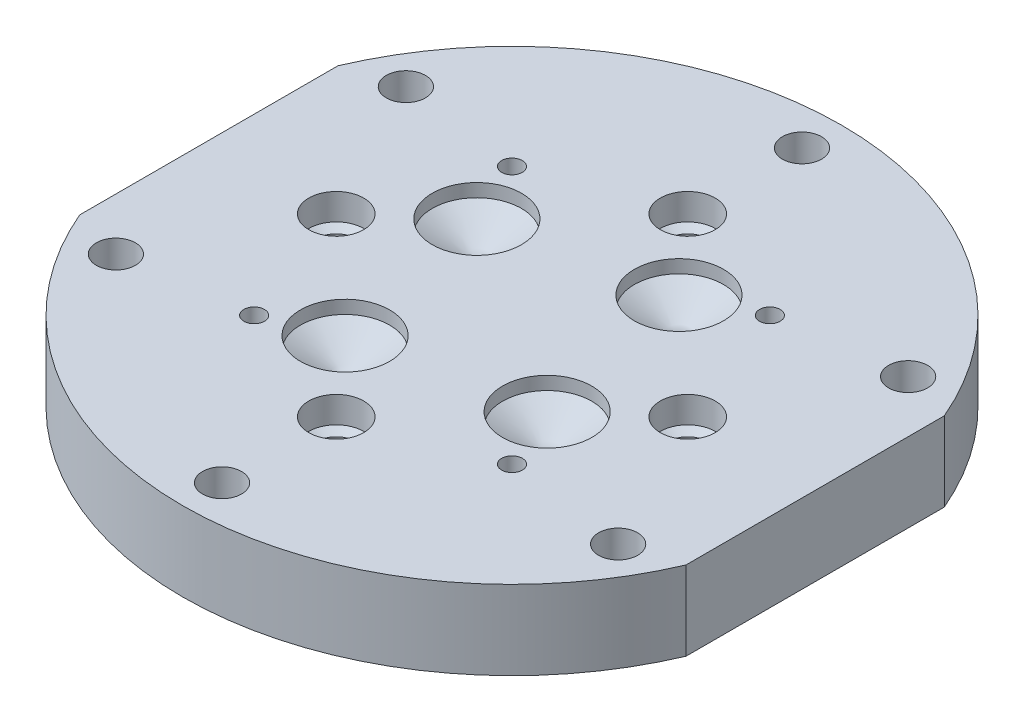
SolidWorks part; units mm, degrees
material "Copper"
ref_plane "Front Plane" through (0, 0, 0) normal (0, 0, 1) x (1, 0, 0)
ref_plane "Top Plane" through (0, 0, 0) normal (0, 1, 0) x (1, 0, 0)
ref_plane "Right Plane" through (0, 0, 0) normal (1, 0, 0) x (0, 0, -1)
ref_axis "Y Axis" through (0, 0.1588, 0) along (0, -1, 0)
sketch "outer" plane through (0, 0, 0) normal (0, 1, 0) x (1, 0, 0)
  circle A0 centre (0, 0) radius 19.05
  dimension "D1" = 38.1
extrude "Body" add sketch "outer" against normal blind 4.572
sketch "Screw Position" plane through (0, 0, 0) normal (0, 1, 0) x (1, 0, 0)
  point P0 (0, -16.764)
  dimension "D1" = 16.764
hole_wizard "#4-40 Tapped Hole" positions "Sketch12" profile "Sketch13" tap size "#4-40" standard "ANSI Inch" end condition through all
sketch "Sketch12" plane through (0, 0, 0) normal (0, 1, 0) x (1, 0, 0)
  point P0 (0, -16.764)
sketch "Sketch13" plane through (0, 0, 16.764) normal (1, 0, 0) x (0, 0, 1)
  line L0 (0, 0) -> (0, 4.572)
  line L1 (0, 4.572) -> (1.1303, 4.572)
  line L2 (1.1303, 4.572) -> (1.1303, 0)
  line L5 (1.1303, 0) -> (0, 0)
  line L11 (0, -6.35) -> (0, 107.95) construction
  dimension "Thru Tap Drill Dia." = 2.2606
  dimension "Thru Tap Drill Depth" = 4.572
cosmetic thread "Hole Thread3" parameters "D2"=2.8448
pattern_circular "Screw Holes" count 6 over 360 about axis through (0, 0.1588, 0) along (0, -1, 0) of "#4-40 Tapped Hole"
sketch "inner" plane through (0, 0, 0) normal (0, 1, 0) x (1, 0, 0)
  circle A0 centre (0, 0) radius 11.938
  dimension "D1" = 23.876
sketch "Inner Screw Position" plane through (0, 0, 0) normal (0, 1, 0) x (1, 0, 0)
  point P0 (-7.4536, 7.4536)
  dimension "D1" = 10.541
hole_wizard "#0-80 Tapped Hole" positions "Sketch34" profile "Sketch35" tap size "#0-80" standard "ANSI Inch" end condition through all
sketch "Sketch34" plane through (0, 0, 0) normal (0, 1, 0) x (1, 0, 0)
  point P0 (-7.4536, 7.4536)
sketch "Sketch35" plane through (-7.4536, 0, -7.4536) normal (1, 0, 0) x (0, 0, 1)
  line L0 (0, 0) -> (0, 4.572)
  line L1 (0, 4.572) -> (0.5956, 4.572)
  line L2 (0.5956, 4.572) -> (0.5956, 0)
  line L5 (0.5956, 0) -> (0, 0)
  line L11 (0, -6.35) -> (0, 107.95) construction
  dimension "Thru Tap Drill Dia." = 1.1913
  dimension "Thru Tap Drill Depth" = 4.572
cosmetic thread "Hole Thread4" parameters "D2"=1.524
pattern_circular "Inner Screw Holes" count 4 over 360 about axis through (0, 0.1588, 0) along (0, -1, 0) of "#0-80 Tapped Hole"
sketch "IO Hole Location" plane through (0, 0, 0) normal (0, 1, 0) x (1, 0, 0)
  point P0 (0, 10.16)
hole_wizard "#43 (0.089) Diameter Hole1" positions "Sketch36" profile "Sketch37" hole size "#43" standard "ANSI Inch" end condition through all
sketch "Sketch36" plane through (0, 0, 0) normal (0, 1, 0) x (1, 0, 0)
  point P0 (0, 10.16)
sketch "Sketch37" plane through (0, 0, -10.16) normal (1, 0, 0) x (0, 0, 1)
  line L0 (0, 0) -> (0, 4.572)
  line L1 (0, 4.572) -> (1.1303, 4.572)
  line L2 (1.1303, 4.572) -> (1.1303, 0)
  line L5 (1.1303, 0) -> (0, 0)
  line L11 (0, -6.35) -> (0, 107.95) construction
  dimension "Thru Hole Dia." = 2.2606
  dimension "Thru Hole Depth" = 4.572
hole_wizard "1/8 (0.125) Diameter Hole1" positions "Sketch38" profile "Sketch40" hole size "1/8" standard "ANSI Inch"
sketch "Sketch38" plane through (0, 0, 0) normal (0, 1, 0) x (1, 0, 0)
  point P0 (0, 10.16)
sketch "Sketch40" plane through (0, 0, -10.16) normal (1, 0, 0) x (0, 0, 1)
  line L0 (0, 0) -> (0, 2.4779)
  line L1 (0, 2.4779) -> (1.5875, 1.524)
  line L2 (1.5875, 1.524) -> (1.5875, 0)
  line L5 (1.5875, 0) -> (0, 0)
  line L10 (0, 2.4779) -> (-1.5875, 1.524) construction
  line L11 (0, -6.35) -> (0, 107.95) construction
  dimension "Hole Dia." = 3.175
  dimension "Hole Depth" = 1.524
  dimension "Drill Angle" = 118
hole_wizard "1/8 (0.125) Diameter Hole2" positions "Sketch41" profile "Sketch42" hole size "1/8" standard "ANSI Inch"
sketch "Sketch41" plane through (0, -4.572, 0) normal (0, -1, 0) x (-1, 0, 0)
  point P0 (0, 10.16)
sketch "Sketch42" plane through (0, -4.572, -10.16) normal (1, 0, 0) x (0, 0, -1)
  line L0 (0, 0) -> (0, 2.4779)
  line L1 (0, 2.4779) -> (1.5875, 1.524)
  line L2 (1.5875, 1.524) -> (1.5875, 0)
  line L5 (1.5875, 0) -> (0, 0)
  line L10 (0, 2.4779) -> (-1.5875, 1.524) construction
  line L11 (0, -6.35) -> (0, 107.95) construction
  dimension "Hole Dia." = 3.175
  dimension "Hole Depth" = 1.524
  dimension "Drill Angle" = 118
pattern_circular "IO Holes Pattern" count 4 over 360 about axis through (0, 0.1588, 0) along (0, -1, 0) of "#43 (0.089) Diameter Hole1", "1/8 (0.125) Diameter Hole1", "1/8 (0.125) Diameter Hole2"
sketch "Post Bottom Location" plane through (0, 0, 0) normal (0, 1, 0) x (1, 0, 0)
  point P0 (3.81, 5.842)
  dimension "D1" = 3.81
  dimension "D2" = 5.842
hole_wizard "13/64 (0.20313) Diameter Hole1" positions "Sketch44" profile "Sketch45" hole size "13/64" standard "ANSI Inch"
sketch "Sketch44" plane through (0, 0, 0) normal (0, 1, 0) x (1, 0, 0)
  point P7 (3.81, 5.842)
sketch "Sketch45" plane through (3.81, 0, -5.842) normal (1, 0, 0) x (0, 0, 1)
  line L0 (0, 0) -> (0, 2.3121)
  line L1 (0, 2.3121) -> (2.5798, 0.762)
  line L2 (2.5798, 0.762) -> (2.5798, 0)
  line L5 (2.5798, 0) -> (0, 0)
  line L10 (0, 2.3121) -> (-2.5798, 0.762) construction
  line L11 (0, -6.35) -> (0, 107.95) construction
  dimension "Hole Dia." = 5.1595
  dimension "Hole Depth" = 0.762
  dimension "Drill Angle" = 118
pattern_circular "Post Bottoms" count 4 over 360 about axis through (0, 0.1588, 0) along (0, -1, 0) of "13/64 (0.20313) Diameter Hole1"
sketch "Flat Cut Sketch" plane through (0, 0, 0) normal (0, 1, 0) x (1, 0, 0)
  line L0 (-20.574, 19.05) -> (-17.526, 19.05)
  line L1 (20.574, -19.05) -> (17.526, -19.05)
  line L2 (20.574, -19.05) -> (20.574, 19.05)
  line L3 (20.574, 19.05) -> (17.526, 19.05)
  line L4 (17.526, -19.05) -> (17.526, 19.05)
  line L5 (20.574, -19.05) -> (17.526, 19.05) construction
  line L6 (20.574, 19.05) -> (17.526, -19.05) construction
  line L7 (-20.574, 19.05) -> (-20.574, -19.05)
  line L8 (-20.574, -19.05) -> (-17.526, -19.05)
  line L9 (-17.526, 19.05) -> (-17.526, -19.05)
  line L10 (-20.574, 19.05) -> (-17.526, -19.05) construction
  line L11 (-20.574, -19.05) -> (-17.526, 19.05) construction
  circle A0 centre (0, 0) radius 19.05 construction
  point P1 (19.05, 0)
  point P3 (19.05, 0)
  point P11 (-19.05, 0)
  point P12 (-19.05, 0)
  point P17 (0, 0)
  dimension "D2" = 38.1
  dimension "D3" = 2
extrude "Flat Cut" cut sketch "Flat Cut Sketch" against normal through all and the other way through all
equation "\"outer_d\"= 3 / 2in"
equation "\"screw_r\"= 0.66in"
equation "\"inner_d\"= 0.940in"
equation "\"bottom_h\" = 0.18in"
equation "\"pocket_h\"= 0.060in"
equation "\"screw_inner_r\"= 0.415in"
equation "\"io_r\"= 0.4in"
equation "\"D1@outer\" = \"outer_d\""
equation "\"D1@Body\" = \"bottom_h\""
equation "\"D1@inner\" = \"inner_d\""
equation "\"D1@Screw Position\" = \"screw_r\""
equation "\"D1@Inner Screw Position\" = \"screw_inner_r\""
equation "\"D1@IO Hole Location\"=\"io_r\""
equation "\"post_x\"= 0.15in"
equation "\"post_z\"= 0.23in"
equation "\"post_bottom_h\"= 0.03in"
equation "\"cut\"= 0.06in"
equation "\"D2@Flat Cut Sketch\"=\"outer_d\""
equation "\"D1@Flat Cut Sketch\"=2 * \"cut\""
equation "\"post_size\"= 0.201in"
equation "\"D1@Post Bottom Location\"=\"post_x\""
equation "\"D2@Post Bottom Location\"=\"post_z\""
